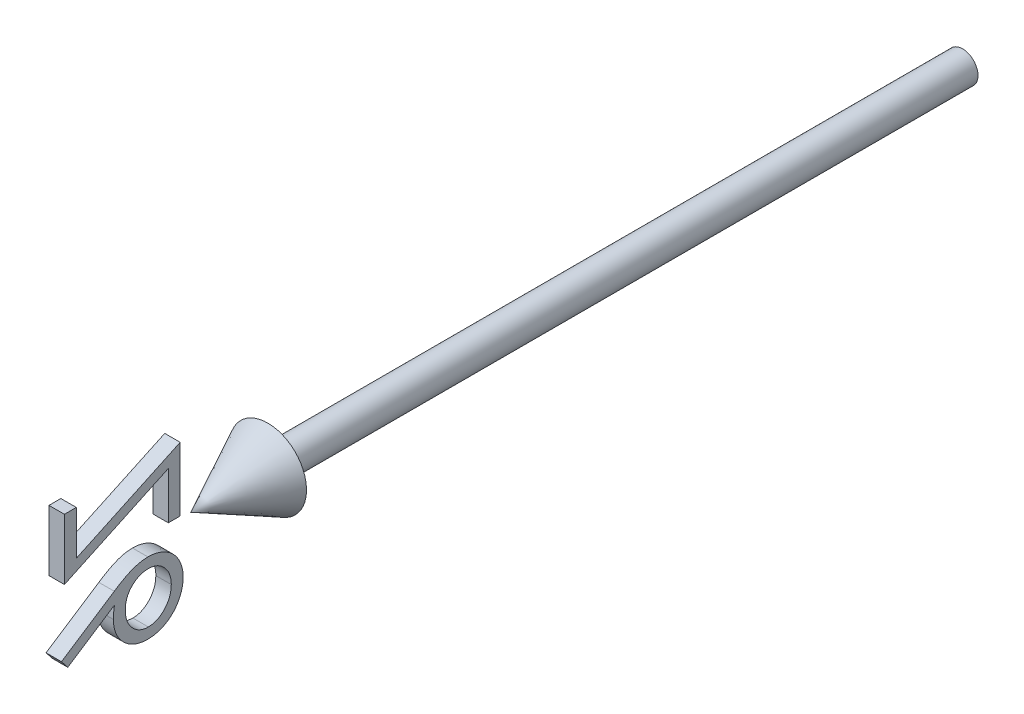
SolidWorks part; units mm, degrees
ref_plane "Front Plane" through (0, 0, 0) normal (0, 0, 1) x (1, 0, 0)
ref_plane "Top Plane" through (0, 0, 0) normal (0, 1, 0) x (1, 0, 0)
ref_plane "Right Plane" through (0, 0, 0) normal (1, 0, 0) x (0, 0, -1)
sketch "Sketch2" plane through (0, 0, 0) normal (0, 1, 0) x (1, 0, 0)
  line L0 (0, 41.95) -> (0, -114.4521) construction
  line L1 (-36.8894, 0) -> (41.4965, 0) construction
  line L2 (0, -100) -> (5, -90)
  line L3 (5, -90) -> (2, -90)
  line L4 (2, -90) -> (2, 0)
  line L5 (2, 0) -> (0, 0)
  line L6 (0, 0) -> (0, -100)
  dimension "D1" = 100
  dimension "D2" = 2
  dimension "D3" = 10
  dimension "D4" = 5
revolve "Revolve1" add sketch "Sketch2" angle 360 about L0
sketch "Sketch3" plane through (0, 0, 0) normal (1, 0, 0) x (0, -1, 0)
  line L0 (0, -101.5706) -> (0, -127.8138) construction
  line L1 (-10.1124, -102.3675) -> (14.1256, -102.3675) construction
  text T0 "Z6\r\n" font "Century Gothic" height 15
extrude "Boss-Extrude1" add sketch "Sketch3" against normal blind 1 and the other way blind 1 separate body
equation "\"frame_arrow_length\"=100"
equation "\"D1@Sketch2\"=\"frame_arrow_length\""
equation "\"frame_arrow_odA\"=4"
equation "\"D2@Sketch2\"=\"frame_arrow_odA\"/2"
equation "\"frame_arrow_head_od\"=5"
equation "\"D4@Sketch2\"=\"frame_arrow_head_od\""
equation "\"frame_arrow_head_length\"=10"
equation "\"D3@Sketch2\"=\"frame_arrow_head_length\""
equation "\"tvarobot_theta1\"=30"
equation "\"link0_ringA_odA\"= 40"
equation "\"link0_ringA_odB\"= 25"
equation "\"link0_ringA_id\"= 20"
equation "\"link0_ringA_thickness\"= (\"link0_ringA_odB\" - \"link0_ringA_id\")/2"
equation "\"link0_ringA_height\"= 3"
equation "\"link0_ringA_heightA\"= 1.5"
equation "\"link0_ringA_heightB\"=\"link0_ringA_height\"-\"link0_ringA_heightA\""
equation "\"link0_ringB_odA\"= 40"
equation "\"link0_ringB_odB\"= 29"
equation "\"link0_ringB_id\"= \"link0_shaftA_bearing_id\"+1"
equation "\"link0_ringB_thickness\"= (\"link0_ringB_odB\" - \"link0_ringB_id\")/2"
equation "\"link0_ringB_height\"= 3"
equation "\"link0_ringB_heightA\"= 1.5"
equation "\"link0_ringB_heightB\"=\"link0_ringB_height\"-\"link0_ringB_heightA\""
equation "\"link0_shaftA_bearing_od\"=27"
equation "\"link0_shaftA_bearing_id\"=20"
equation "\"link0_shaftA_thrust_bearing_od\"=35"
equation "\"link0_shaftA_thrust_bearing_id\"=20.04"
equation "\"link0_shaftA_retaining_ring_id\"=18.5"
equation "\"link0_shaftA_retaining_ring_groove_width\"=1.5"
equation "\"link0_shaftA_spline_length\"=8.0"
equation "\"link0_shaftA_spline_depth\"=1.0"
equation "\"link0_shaftA_spline_width\"=4.0"
equation "\"link0_shaftA_odA\"=\"link0_shaftA_bearing_id\""
equation "\"link0_shaftA_odB\"=35"
equation "\"link0_shaftA_odC\"=\"link0_shaftA_bearing_id\""
equation "\"link0_shaftA_odD\"=\"link0_shaftA_odC\"-2*\"link0_shaftA_spline_depth\""
equation "\"link0_shaftA_odE\"=\"link0_shaftA_bearing_id\""
equation "\"link0_shaftA_odF\"=\"link0_shaftA_odE\"-2*\"link0_shaftA_spline_depth\""
equation "\"link0_shaftA_idA\"=10"
equation "\"link0_shaftA_idB\"=6"
equation "\"link0_shaftA_length\"=39.5"
equation "\"link0_shaftA_lengthA\"=8.0"
equation "\"link0_shaftA_lengthB\"=12.0"
equation "\"link0_shaftA_lengthC\"=35.0"
equation "\"link0_shaftA_lengthD\"=39.0"
equation "\"link0_shaftA_lengthE\"=\"link0_shaftA_length\"-\"link0_shaftA_lengthD\""
equation "\"link0_shaftA_offsetX\"=11"
equation "\"link0_shaftA_offsetY\"=0"
equation "\"link0_shaftA_bolt_pattern_dia\"=14"
equation "\"link0_motor_center_dist\"=26"
equation "\"link0_46t_pulley_spline_length\"=8"
equation "\"link0_46t_pulley_spline_depth\"=\"link0_shaftA_spline_depth\"*1.025"
equation "\"link0_46t_pulley_spline_width\"=\"link0_shaftA_spline_width\"*1.05"
equation "\"link0_46t_pulley_idA\"=\"link0_shaftA_bearing_id\"*1.025"
equation "\"link0_46t_pulley_idB\"=\"link0_46t_pulley_idA\"-2*\"link0_46t_pulley_spline_depth\""
equation "\"link0_shaftB_spline_length\"=10"
equation "\"link0_shaftB_spline_depth\"=1.0"
equation "\"link0_shaftB_spline_width\"=1.25"
equation "\"link0_shaftB_length\"=7"
equation "\"link0_shaftB_lengthA\"=1.5"
equation "\"link0_shaftB_lengthB\"=2.75"
equation "\"link0_shaftB_odA\"=32"
equation "\"link0_shaftB_odB\"=22"
equation "\"link0_shaftB_odC\"=20"
equation "\"link0_shaftB_idA\"=10"
equation "\"link0_shaftB_bolt_diameter\"=19"
equation "\"link0_shaftB_bearing_od\"=27"
equation "\"link0_shaftB_bearing_id\"=20"
equation "\"link0_motor_length\"=46.5"
equation "\"link0_motor_width\"=28.5"
equation "\"link0_motor_height\"=34"
equation "\"link0_motor_offset\"=8"
equation "\"link0_shellA_thickness\"=2.5"
equation "\"link0_shellB_thickness\"=\"link0_shellA_thickness\""
equation "\"link0_plateA_shellA_height\"=48"
equation "\"link0_shellA_width\" =\"link0_plateA_width\""
equation "\"link0_shellA_height\" = \"link0_plateA_shellA_height\"-\"link0_plateA_height\""
equation "\"link0_shellA_length\" = \"link0_plateA_lengthB\" "
equation "\"link0_shellB_length\"=\"link0_shellA_length\""
equation "\"link0_shellA_radius\" = 0.375*25.4"
equation "\"link0_shellA_radiusA\"= \"link0_plateA_radiusA\""
equation "\"link0_shellA_radiusB\"= \"link0_plateA_radiusB\""
equation "\"link0_shellA_radiusC\"= 3"
equation "\"link0_postA_height\"=7"
equation "\"link0_postA_width\"=16"
equation "\"link0_postA_length\"=20"
equation "\"link0_postA_posX\"=22"
equation "\"link0_postA_posY\"=17.5"
equation "\"link0_postA_pocket_width\"=6.0"
equation "\"link0_postA_pocket_length\"=2.5"
equation "\"link0_postA_pocket_depth\"=9"
equation "\"link0_postA_pocket_posZ\"=10"
equation "\"link0_postB_height\"=7"
equation "\"link0_postB_width\"=16"
equation "\"link0_postB_length\"=20"
equation "\"link0_postB_posX\"=22"
equation "\"link0_postB_posY\"=17.5"
equation "\"link0_postB_id\"=3.0"
equation "\"link0_postB_pocket_width\"=6.0"
equation "\"link0_postB_pocket_length\"=2.5"
equation "\"link0_postB_pocket_depth\"=9"
equation "\"link0_postB_pocket_posZ\"=10"
equation "\"link0_postC_height\"=7"
equation "\"link0_postC_width\"=16"
equation "\"link0_postC_length\"=20"
equation "\"link0_postC_posX\"=22"
equation "\"link0_postC_posY\"=17.5"
equation "\"link0_postC_id\"=3.0"
equation "\"link0_postC_pocket_width\"=6.0"
equation "\"link0_postC_pocket_length\"=2.5"
equation "\"link0_postC_pocket_depth\"=9"
equation "\"link0_postC_pocket_posZ\"=10"
equation "\"link0_postD_height\"=7"
equation "\"link0_postD_width\"=16"
equation "\"link0_postD_length\"=20"
equation "\"link0_postD_posX\"=22"
equation "\"link0_postD_posY\"=17.5"
equation "\"link0_postD_id\"=3.0"
equation "\"link0_postD_pocket_width\"=6.0"
equation "\"link0_postD_pocket_length\"=3.0"
equation "\"link0_postD_pocket_depth\"=9"
equation "\"link0_postD_pocket_posZ\"=10"
equation "\"link0_postE_height\"=5"
equation "\"link0_postE_width\"=16"
equation "\"link0_postE_length\"=\"link0_plateE_lengthA\"-\"link0_lip_height\""
equation "\"link0_postE_posZ\"=22"
equation "\"link0_postE_posX\"=17.5"
equation "\"link0_postE_posY\"=22"
equation "\"link0_postE_id\"=3.0"
equation "\"link0_postE_cbore_id\"=6.5"
equation "\"link0_postE_hole_id\"=3"
equation "\"link0_postF_posZ\"=22"
equation "\"link0_postF_posX\"=17.5"
equation "\"link0_postF_posY\"=\"link0_plateB_lengthA\"+4"
equation "\"link0_postF_id\"=3.0"
equation "\"link0_postF_cbore_id\"=6.5"
equation "\"link0_postF_hole_id\"=3"
equation "\"link0_postG_posZ\"=22"
equation "\"link0_postG_posX\"=17.5"
equation "\"link0_postG_posY\"=\"link0_plateB_lengthA\"+12"
equation "\"link0_postG_id\"=3.0"
equation "\"link0_postG_cbore_id\"=6.5"
equation "\"link0_postG_hole_id\"=3"
equation "\"link0_postHIJ_posY\"=6"
equation "\"link0_postH_posX\"=28"
equation "\"link0_postH_posY\"=20"
equation "\"link0_postH_posZ\"=20"
equation "\"link0_postH_length\"=10"
equation "\"link0_postI_posX\"=28"
equation "\"link0_postI_posY\"=20"
equation "\"link0_postI_posZ\"=135"
equation "\"link0_postI_length\"=10"
equation "\"link0_postJ_posX\"=28"
equation "\"link0_postJ_posY\"=20"
equation "\"link0_postJ_posZ\"=175"
equation "\"link0_postJ_length\"=10"
equation "\"link0_postK_posX\"=28"
equation "\"link0_postK_posY\"=20"
equation "\"link0_postK_posZ\"=175"
equation "\"link0_postK_length\"=10"
equation "\"link0_postL_posX\"=28"
equation "\"link0_postL_posY\"=20"
equation "\"link0_postL_posZ\"=135"
equation "\"link0_postL_length\"=10"
equation "\"link0_postM_posX\"=28"
equation "\"link0_postM_posY\"=20"
equation "\"link0_postM_posZ\"=35"
equation "\"link0_postM_length\"=10"
equation "\"link0_plateA_lengthA\"=30"
equation "\"link0_plateA_lengthB\"=150"
equation "\"link0_plateA_lengthC\"=30"
equation "\"link0_plateA_length\"=\"link0_plateA_lengthA\"+\"link0_plateA_lengthB\"+\"link0_plateA_lengthC\""
equation "\"link0_plateA_width\"=  68"
equation "\"link0_plateA_height\"= \"link0_plateA_radiusA\""
equation "\"link0_plateA_thickness\"=\"link0_shellA_thickness\""
equation "\"link0_plateA_radius\"= 9.5"
equation "\"link0_plateA_radiusA\"= 18"
equation "\"link0_plateA_radiusB\"= 18"
equation "\"link0_plateA_radiusC\"= 3"
equation "\"link0_plateB_length\"= 40"
equation "\"link0_plateB_width\"= \"link0_plateA_width\"*1.005"
equation "\"link0_plateB_height\"= \"link0_plateA_shellA_height\"*1.005"
equation "\"link0_plateB_lengthA\"=\"link0_lip_height\"+\"link0_plateD_thickness\"+\"link0_motor_mount_thickness\""
equation "\"link0_plateB_lengthB\"=\"link0_plateB_height\"-\"link0_plateB_lengthA\""
equation "\"link0_plateB_radiusA\"= \"link0_plateA_radiusA\""
equation "\"link0_plateB_radiusB\"= \"link0_plateA_radiusB\""
equation "\"link0_plateB_radiusC\"= 3"
equation "\"link0_plateB_idA\"=\"link0_shaftA_odC\"+1"
equation "\"link0_plateB_idB\"=\"link0_shaftA_bearing_od\"-2"
equation "\"link0_plateB_idC\"=\"link0_shaftA_bearing_od\"*1.005"
equation "\"link0_plateB_idD\"=\"link0_shaftA_thrust_bearing_od\"+1 "
equation "\"link0_plateB_depthA\"=1.0"
equation "\"link0_plateB_depthB\"=2.0"
equation "\"link0_plateB_depthC\"=8"
equation "\"link0_plateB_depthD\"=\"link0_plateB_length\"-\"link0_lip_height\"-\"link0_plateD_thickness\" "
equation "\"link0_plateC_length\"=\"link0_plateB_length\""
equation "\"link0_plateC_width\"= \"link0_plateB_width\""
equation "\"link0_plateC_height\"= .1*25.4"
equation "\"link0_plateA_hole_od\" = 0.1*25.4"
equation "\"link0_plateA_hole_delx\" = 0.5*25.4"
equation "\"link0_plateA_hole_delz\" = 0.75*25.4"
equation "\"link0_plateA_hole_offx\" = 0.0*25.4"
equation "\"link0_plateA_hole_offz\" = \"link0_plateA_length\"/2"
equation "\"link0_plateB_hole_od\" = 0.1*25.4"
equation "\"link0_plateB_hole_delx\"= 0.75*25.4"
equation "\"link0_plateB_hole_delz\"= 0.75*25.4"
equation "\"link0_plateB_hole_offx\"= 0.0*25.4"
equation "\"link0_plateB_hole_offz\"= 0.0*25.4"
equation "\"link0_plateC_hole_od\"= 0.1*25.4"
equation "\"link0_plateC_hole_delx\"= 0.75*25.4"
equation "\"link0_plateC_hole_delz\"= 0.75*25.4"
equation "\"link0_plateC_hole_offx\"= 0.0*25.4"
equation "\"link0_plateC_hole_offz\"= 0.0*25.4"
equation "\"link0_plateD_height\"=\"link0_plateB_height\"-2*\"link0_shellA_thickness\""
equation "\"link0_plateD_width\"=\"link0_plateB_width\"-2*\"link0_shellA_thickness\""
equation "\"link0_plateD_thickness\"=10"
equation "\"link0_plateD_radiusA\"=\"link0_plateB_radiusA\"-\"link0_shellA_thickness\""
equation "\"link0_plateD_odA\"= .375*25.4"
equation "\"link0_plateD_odB\"= .375*25.4"
equation "\"link0_plateD_bearing_id\"=20"
equation "\"link0_plateD_bearing_od\"=27"
equation "\"link0_plateE_radiusA\"=\"link0_plateA_radiusA\""
equation "\"link0_plateE_radiusB\"=\"link0_plateA_radiusB\""
equation "\"link0_plateE_radiusC\"=8.0"
equation "\"link0_plateE_length\"=30"
equation "\"link0_plateE_lengthA\"=16"
equation "\"link0_plateE_height\"=\"link0_plateB_height\""
equation "\"link0_plateE_width\"=\"link0_plateB_width\""
equation "\"link0_plateE_odA\"=\"gantry_coupler_id\"*0.99"
equation "\"link0_plateE_idA\"=\"link0_plateE_odA\"-20.0"
equation "\"link0_plateE_spline_depth\"=\"link0_poleA_spline_depth\"*1.05"
equation "\"link0_plateE_spline_width\"=\"link0_poleA_spline_width\"*1.075"
equation "\"link0_plateE_spline_length\"=\"link0_poleA_spline_length\""
equation "\"link0_plateE_coupler_length\"=46"
equation "\"link0_lip_height\"=5.0"
equation "\"link0_lip_thickness\"=2.0"
equation "\"link0_motor_mount_thickness\"=8.0"
equation "\"link0_motor_mount_idA\"=22"
equation "\"link0_motor_mount_idB\"=\"link0_shaftB_bearing_od\"*1.005"
equation "\"link0_motor_mount_idC\"=\"link0_shaftB_bearing_od\"-2"
equation "\"link0_motor_mount_depthA\"=5.5"
equation "\"link0_motor_mount_height\"=\"link0_plateD_height\""
equation "\"link0_motor_mount_width\"=\"link0_plateD_width\""
equation "\"link0_motor_mountL_height\"=36"
equation "\"link0_motor_mountL_heightA\"=12"
equation "\"link0_motor_mountL_length\"=50"
equation "\"link0_motor_mountL_lengthA\"=36"
equation "\"gantry_coupler_od\"=25.4*2.0"
equation "\"gantry_coupler_id\"=1.645*25.4"
equation "\"gantry_coupler_offsetX\"=\"link0_plateE_width\"/2"
equation "\"link0_poleA_odA\"=20"
equation "\"link0_poleA_odB\"=36"
equation "\"link0_poleA_idA\"=\"link0_poleA_odA\"-2*\"link0_poleA_thickness\""
equation "\"link0_poleA_idB\"=(\"link0_plateE_idA\"/2+1.5*\"link0_lip_thickness\")*1.04"
equation "\"link0_poleA_thickness\"=3.5"
equation "\"link0_poleA_length\"=100"
equation "\"link0_poleA_lengthA\"=18.5"
equation "\"link0_poleA_lengthB\"=80"
equation "\"link0_poleA_gasket_thickness\"=1.5"
equation "\"link0_poleA_spline_depth\"=1.0"
equation "\"link0_poleA_spline_width\"=4.0"
equation "\"link0_poleA_spline_length\"=10.0"
equation "\"link1_plateB_length\"=30"
equation "\"link1_lip_height\"=\"link0_lip_height\""
equation "\"link0_tension_plateA_width\"=12"
equation "\"link0_tension_plateA_lengthA\"=10.5"
equation "\"link0_tension_plateB_width\"=\"link0_tension_plateA_width\""
equation "\"link0_tension_plateB_lengthA\"=\"link0_tension_plateA_lengthA\""
equation "\"link0_tension_wheelA_posZ\"=7"
equation "\"link0_tension_wheelA_posX\"=\"link0_plateD_height\"/2-\"link0_tension_plateA_lengthA\""
equation "\"link0_m2_clear_hole_id\"=2.35"
equation "\"link0_m2_insert_hole_id\"=2.5"
equation "\"link0_m2_tap_hole_id\"=1.75"
equation "\"link0_m2_nut_socket_width\"=4.25"
equation "\"link0_m2_nut_socket_depth\"=2.5"
equation "\"link0_m2_cbore_id\"=3.75"
equation "\"link0_m2_cbore_depth\"=7"
equation "\"link0_m2_5_clear_hole_id\"=2.75"
equation "\"link0_m2_5_insert_hole_id\"=2.75"
equation "\"link0_m2_5_tap_hole_id\"=2.25"
equation "\"link0_m2_5_nut_socket_width\"=5.25"
equation "\"link0_m2_5_nut_socket_depth\"=2.5"
equation "\"link0_m2_5_cbore_id\"=4.75"
equation "\"link0_m2_5_cbore_depth\"=2.5"
equation "\"link0_m2_5_insert_access_length\"=6.0"
equation "\"link0_m2_5_insert_access_width\"=3.0"
equation "\"link0_m3_clear_hole_id\"=3.25"
equation "\"link0_m3_insert_hole_id\"=3"
equation "\"link0_m3_tap_hole_id\"=2.75"
equation "\"link0_m3_nut_socket_width\"=5.75"
equation "\"link0_m3_nut_socket_depth\"=4.0"
equation "\"link0_m3_cbore_id\"=5.75"
equation "\"link0_m3_cbore_depth\"=3.5"
equation "\"link0_m3_insert_access_length\"=4.5"
equation "\"link0_m3_insert_access_width\"=3.5"
equation "\"link0_rpi_mount_height\"=6"
equation "\"link0_rpi_mount_width\"=49"
equation "\"link0_rpi_mount_length\"=58"
equation "\"link0_rpi_mount_post_od\"=6"
equation "\"link0_rpi_mount_posZ\"=72"
equation "\"link0_rpi_mount_posX\"=11.5"
equation "\"link0_mcu_mount_height\"=5"
equation "\"link0_mcu_mount_width\"=49"
equation "\"link0_mcu_mount_length\"=58"
equation "\"link0_mcu_mount_post_od\"=6"
equation "\"link0_mcu_mount_posZ\"=164"
equation "\"link0_mcu_mount_posX\"=4"
equation "\"link0_pwr_mount_height\"=4"
equation "\"link0_pwr_mount_width\"=15.75"
equation "\"link0_pwr_mount_length\"=75.75"
equation "\"link0_pwr_mount_post_od\"=6"
equation "\"link0_pwr_mount_posZ\"=75"
equation "\"link0_pwr_mount_posX\"=16"
equation "\"link0_pwr_board_height\"=6"
equation "\"link0_pwr_board_width\"=21"
equation "\"link0_pwr_board_length\"=80"
